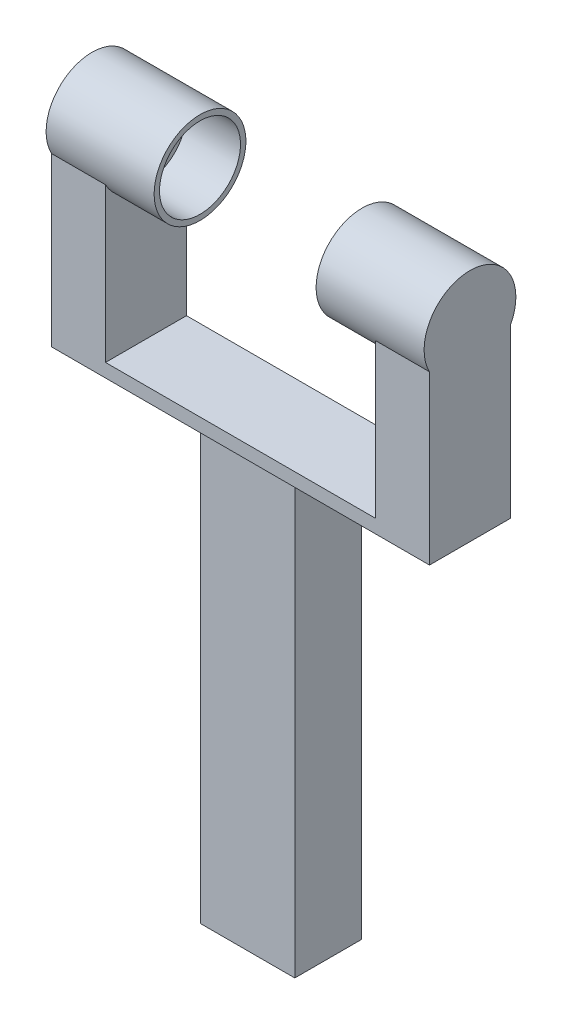
SolidWorks part; units mm, degrees
ref_plane "Front Plane" through (0, 0, 0) normal (0, 0, 1) x (1, 0, 0)
ref_plane "Top Plane" through (0, 0, 0) normal (0, 1, 0) x (1, 0, 0)
ref_plane "Right Plane" through (0, 0, 0) normal (1, 0, 0) x (0, 0, -1)
sketch "Sketch1" plane through (0, 0, 0) normal (0, 1, 0) x (1, 0, 0)
  line L1 (-70, 15) -> (70, 15)
  line L2 (-70, 15) -> (-70, -15)
  line L3 (-70, -15) -> (70, -15)
  line L4 (70, 15) -> (70, -15)
  line L5 (-70, 15) -> (70, -15) construction
  line L6 (-70, -15) -> (70, 15) construction
  point P0 (0, 0)
  dimension "D1" = 140
  dimension "D2" = 30
extrude "Boss-Extrude1" add sketch "Sketch1" against normal blind 5
sketch "Sketch2" plane through (0, 0, 0) normal (0, 1, 0) x (1, 0, 0)
  line L0 (-70, -15) -> (70, -15) construction
  line L1 (-70, 15) -> (-50, 15)
  line L2 (-70, 15) -> (-70, -15)
  line L3 (-70, -15) -> (-50, -15)
  line L4 (-50, 15) -> (-50, -15)
  line L6 (70, 15) -> (50, 15)
  line L7 (70, 15) -> (70, -15)
  line L8 (70, -15) -> (50, -15)
  line L9 (50, 15) -> (50, -15)
  dimension "D1" = 20
  dimension "D2" = 20
extrude "Extrude-Thin1" add sketch "Sketch2" along normal blind 80 thin thin type one direction reverse wall 2
fillet "Fillet1" radius 15 4 edges at (-60, 80, -15) (-60, 80, 15) (60, 80, -15) (60, 80, 15) conic radius 10
sketch "Sketch3" plane through (-70, 0, 0) normal (-1, 0, 0) x (0, 0, 1)
  line L0 (-15, 65) -> (0, 65) construction
  line L1 (0, 65) -> (0, 80) construction
  circle A0 centre (0, 65) radius 15
  spline S0 degree 2 poles (2431.7772, -1673.5343) (126.0649, 115.2414) (-6.0494, 79.2917) (-9.3181, 78.4023) (-11.3602, 76.3606) (-13.4028, 74.3184) (-14.2928, 71.0453) (-50.189, -60.9592) (1736.054, -2368.5113) knots -12.439437 -12.439437 -12.439437 0.25 0.25 0.5 0.5 0.75 0.75 13.440356 13.440356 13.440356 only from (0, 80) to (-15, 65) construction
  spline S1 degree 2 poles (0, 80) (-3.4465, 80) (-6.0494, 79.2917) (-9.3181, 78.4023) (-11.3602, 76.3606) (-13.4028, 74.3184) (-14.2928, 71.0453) (-15, 68.4448) (-15, 65) knots 0 0 0 0.25 0.25 0.5 0.5 0.75 0.75 1 1 1 construction
extrude "Extrude-Thin2" add sketch "Sketch3" against normal blind 40 thin thin type one direction wall 2
mirror "Mirror1" about plane through (0, 0, 0) normal (1, 0, 0) of "Extrude-Thin2"
sketch "Sketch4" plane through (0, -5, 0) normal (0, -1, 0) x (1, 0, 0)
  line L1 (-17.5, -12.395) -> (17.5, -12.395)
  line L2 (-17.5, -12.395) -> (-17.5, 12.395)
  line L3 (-17.5, 12.395) -> (17.5, 12.395)
  line L4 (17.5, -12.395) -> (17.5, 12.395)
  line L5 (-17.5, -12.395) -> (17.5, 12.395) construction
  line L6 (-17.5, 12.395) -> (17.5, -12.395) construction
  point P0 (0, 0)
  dimension "D1" = 35
  dimension "D2" = 24.79
extrude "Boss-Extrude2" add sketch "Sketch4" along normal blind 160
